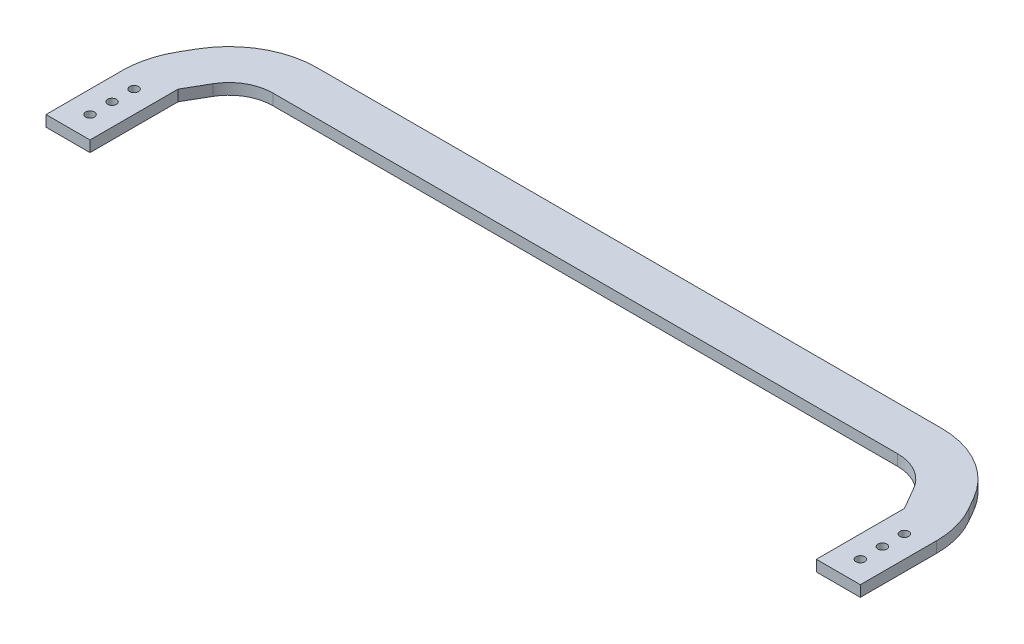
SolidWorks part; units mm, degrees
material "6061-T6 (SS)"
ref_plane "Front" through (0, 0, 0) normal (0, 0, 1) x (1, 0, 0)
ref_plane "Top" through (0, 0, 0) normal (0, 1, 0) x (1, 0, 0)
ref_plane "Right" through (0, 0, 0) normal (1, 0, 0) x (0, 0, -1)
sketch "Sketch1" plane through (0, 0, 0) normal (0, 1, 0) x (1, 0, 0)
  line L0 (-209.55, -50.8) -> (-209.55, 0)
  line L1 (209.55, 0) -> (209.55, -50.8)
  line L2 (209.55, -50.8) -> (234.95, -50.8)
  line L3 (0, 0) -> (0, -66.2098) construction
  line L4 (-209.55, -50.8) -> (-234.95, -50.8)
  line L5 (-234.95, -50.8) -> (-234.95, -6.8059)
  line L6 (234.95, -6.8059) -> (234.95, -50.8)
  line L7 (-209.55, 0) -> (-202.2177, 12.7)
  line L8 (-180.2206, 25.4) -> (180.2206, 25.4)
  line L9 (-209.55, 0) -> (209.55, 0) construction
  line L10 (202.2177, 12.7) -> (209.55, 0)
  line L11 (228.1441, 18.5941) -> (224.2147, 25.4)
  line L12 (180.2206, 50.8) -> (-180.2206, 50.8)
  line L13 (-224.2147, 25.4) -> (-228.1441, 18.5941)
  line L14 (234.95, 6.8059) -> (234.95, -50.8) construction
  line L15 (-234.95, -50.8) -> (-234.95, 6.8059) construction
  arc A6 (193.678, 9.9217) -> (209.55, 0) centre (189.0976, -15.0619) cw construction
  arc A7 (-234.95, 6.8059) -> (-195.425, 57.6814) centre (-50.8541, -95.4263) cw construction
  arc A8 (-195.425, 57.6814) -> (198.2583, 34.9053) centre (-90.3024, -1539.0619) cw construction
  arc A9 (198.2583, 34.9053) -> (234.95, 6.8059) centre (189.0976, -15.0619) cw construction
  arc A10 (-209.55, 0) -> (-184.3292, 32.9285) centre (-50.8541, -95.4263) cw construction
  arc A11 (-184.3292, 32.9285) -> (193.678, 9.9217) centre (-90.3024, -1539.0619) cw construction
  arc A12 (228.1441, 18.5941) -> (234.95, -6.8059) centre (184.15, -6.8059) cw
  arc A13 (224.2147, 25.4) -> (180.2206, 50.8) centre (180.2206, 0) ccw
  arc A14 (-234.95, -6.8059) -> (-228.1441, 18.5941) centre (-184.15, -6.8059) cw
  arc A15 (-180.2206, 50.8) -> (-224.2147, 25.4) centre (-180.2206, 0) ccw
  arc A16 (180.2206, 25.4) -> (202.2177, 12.7) centre (180.2206, 0) cw
  arc A17 (-202.2177, 12.7) -> (-180.2206, 25.4) centre (-180.2206, 0) cw
  dimension "D4" = 30
  dimension "D8" = 50.8
  dimension "D9" = 25.4
  dimension "D1" = 419.1
  dimension "D2" = 50.8
  dimension "D5" = 25.4
  dimension "D6" = 25.4
  dimension "D7" = 25.4
  dimension "D3" = 25.4
extrude "Boss-Extrude1" add sketch "Sketch1" along normal blind 6.35
hole_wizard "#10 Clearance Hole1" positions "Sketch2" profile "Sketch3" hole size "#10" standard "ANSI Inch" end condition through all
sketch "Sketch2" plane through (0, 6.35, 0) normal (0, 1, 0) x (1, 0, 0)
  line L3 (-234.95, -50.8) -> (-222.25, -38.1) construction
  line L4 (-222.25, -38.1) -> (-222.25, -25.4) construction
  line L5 (-222.25, -25.4) -> (-222.25, -12.7) construction
  line L6 (-222.25, -12.7) -> (-209.55, 0) construction
  line L8 (0, 0) -> (0, -50.8) construction
  point P0 (-222.25, -38.1)
  point P2 (-222.25, -25.4)
  point P4 (-222.25, -12.7)
  point P29 (222.25, -12.7)
  point P30 (222.25, -25.4)
  point P31 (222.25, -38.1)
  dimension "D1" = 12.7
sketch "Sketch3" plane through (-222.25, 6.35, 38.1) normal (1, 0, 0) x (0, 0, 1)
  line L0 (0, 0) -> (0, 6.35)
  line L1 (0, 6.35) -> (2.5527, 6.35)
  line L2 (2.5527, 6.35) -> (2.5527, 0)
  line L5 (2.5527, 0) -> (0, 0)
  line L11 (0, -6.35) -> (0, 107.95) construction
  dimension "Thru Hole Dia." = 5.1054
  dimension "Thru Hole Depth" = 6.35
